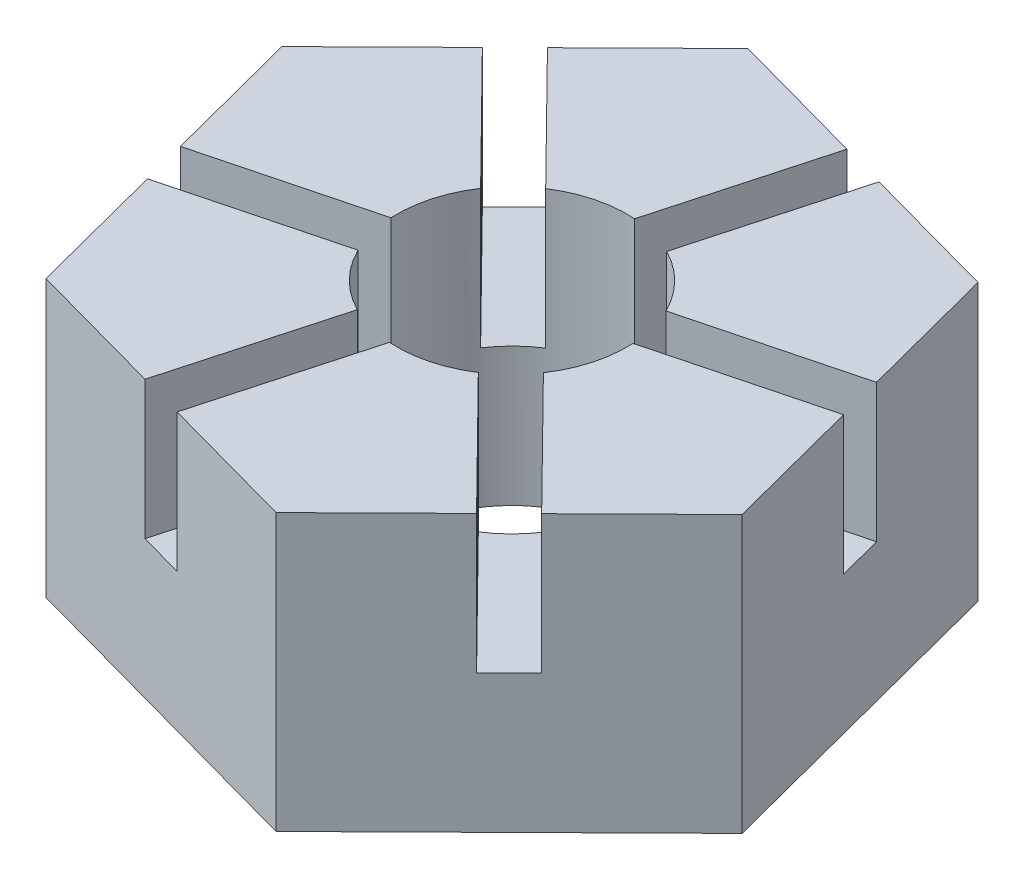
SolidWorks part; units mm, degrees
ref_plane "Front Plane" through (0, 0, 0) normal (0, 0, 1) x (1, 0, 0)
ref_plane "Top Plane" through (0, 0, 0) normal (0, 1, 0) x (1, 0, 0)
ref_plane "Right Plane" through (0, 0, 0) normal (1, 0, 0) x (0, 0, -1)
sketch "Sketch2" plane through (0, 0, 0) normal (0, 1, 0) x (1, 0, 0)
  line L0 (58.7407, 20.4537) -> (22.446, 11.0081)
  line L1 (18.0305, -69.282) -> (69.0153, -19.0261)
  line L2 (69.0153, -19.0261) -> (50.9847, 50.2559)
  line L3 (50.9847, 50.2559) -> (-18.0305, 69.282)
  line L4 (-18.0305, 69.282) -> (-69.0153, 19.0261)
  line L5 (-69.0153, 19.0261) -> (-50.9847, -50.2559)
  line L6 (-50.9847, -50.2559) -> (18.0305, -69.282)
  line L7 (61.2593, 10.7761) -> (24.9646, 1.3304)
  line L8 (58.7407, 20.4537) -> (61.2593, 10.7761)
  line L10 (-18.0305, 69.282) -> (58.7407, 20.4537) construction
  line L11 (18.0305, -69.282) -> (61.2593, 10.7761) construction
  line L12 (39.962, -47.6641) -> (13.6345, -20.9547)
  line L13 (47.0838, -40.6441) -> (20.7563, -13.9348)
  line L14 (-21.2973, -58.4401) -> (-11.3301, -22.2852)
  line L15 (-11.6569, -61.0978) -> (-1.6897, -24.9428)
  line L16 (-61.2593, -10.7761) -> (-24.9646, -1.3304)
  line L17 (-58.7407, -20.4537) -> (-22.446, -11.0081)
  line L18 (-39.962, 47.6641) -> (-13.6345, 20.9547)
  line L19 (-47.0838, 40.6441) -> (-20.7563, 13.9348)
  line L20 (21.2973, 58.4401) -> (11.3301, 22.2852)
  line L21 (11.6569, 61.0978) -> (1.6897, 24.9428)
  circle A0 centre (0, 0) radius 61.9986 construction
  circle A1 centre (0, 0) radius 25
  point P36 (0, 0)
  dimension "D2" = 50
  dimension "D1" = 120
  dimension "D3" = 10
  dimension "D4" = 6
extrude "Boss-Extrude1" add sketch "Sketch2" along normal blind 60 contours A1 L15 L6 L1 L12 | A1 L17 L5 L6 L14 | A1 L19 L4 L5 L16 | A1 L21 L3 L4 L18 | A1 L0 L2 L3 L20 | A1 L13 L1 L2 L7 region at (34.2096, 0, -33.7205) region at (46.3076, 0, 12.7661) region at (-12.0981, 0, -46.4867) region at (12.0981, 0, 46.4867) region at (-46.3076, 0, -12.7661) region at (-34.2096, 0, 33.7205)
extrude "Boss-Extrude2" add sketch "Sketch2<3>" along normal blind 30 contours A1 L14 L6 L15 | A1 L12 L1 L13 | A1 L7 L2 L0 | A1 L20 L3 L21 | A1 L18 L4 L19 | A1 L16 L5 L17 region at (42.0156, 0, -10.9345) region at (11.5383, 0, -41.8538) region at (30.4773, 0, 30.9194) region at (-30.4773, 0, -30.9194) region at (-11.5383, 0, 41.8538) region at (-42.0156, 0, 10.9345)
sketch "Sketch2<3>" plane through (0, 0, 0) normal (0, 1, 0) x (1, 0, 0) same geometry as "Sketch2"
